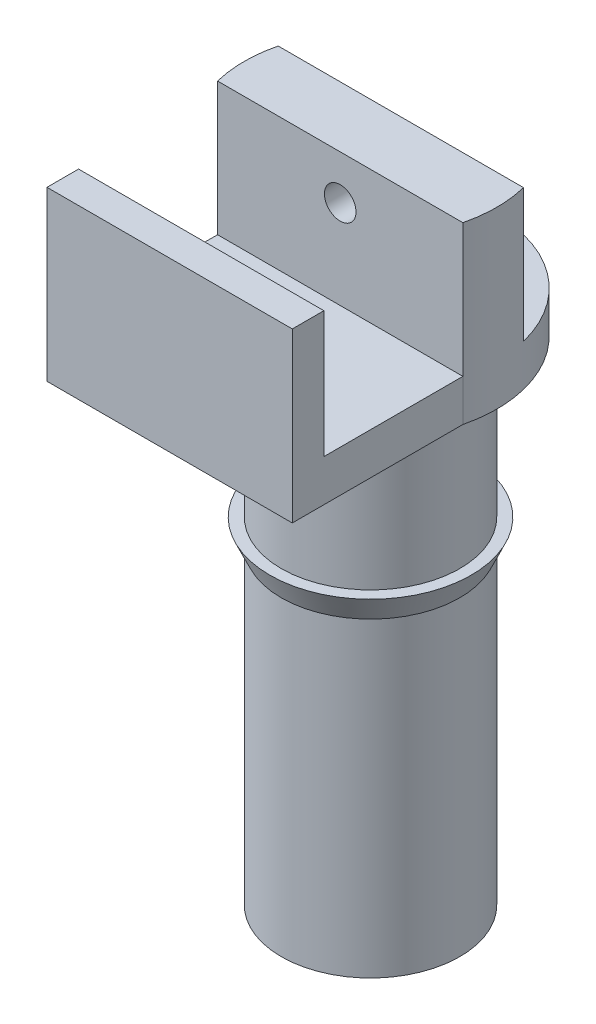
SolidWorks part; units mm, degrees
ref_plane "Front Plane" through (0, 0, 0) normal (0, 0, 1) x (1, 0, 0)
ref_plane "Top Plane" through (0, 0, 0) normal (0, 1, 0) x (1, 0, 0)
ref_plane "Right Plane" through (0, 0, 0) normal (1, 0, 0) x (0, 0, -1)
sketch "Sketch1" plane through (0, 0, 0) normal (0, 1, 0) x (1, 0, 0)
  circle A0 centre (0, 0) radius 17.9497
extrude "Part that goes into base" add sketch "Sketch1" along normal blind 99.06
sketch "Sketch2" plane through (0, 0, 0) normal (0, 0, 1) x (1, 0, 0)
  line L0 (17.9497, 99.06) -> (-17.9497, 99.06) construction
  line L1 (17.9497, 99.06) -> (-17.9497, 99.06)
  line L2 (17.9497, 99.06) -> (17.9497, 67.564) construction
  line L3 (17.9497, 67.564) -> (20.2357, 67.564)
  line L4 (20.2357, 67.564) -> (17.9497, 62.484)
  line L5 (17.9497, 62.484) -> (17.9497, 67.564)
  line L6 (0, 99.06) -> (0, 52.1662) construction
  dimension "D1" = 31.496
  dimension "D2" = 2.286
  dimension "D3" = 5.08
revolve "Clip in mechanism" add sketch "Sketch2" angle 360 about L6 region at (18.7117, 65.8707, 0)
sketch "Sketch3" plane through (0, 99.06, 0) normal (0, 1, 0) x (1, 0, 0)
  circle A0 centre (0, 0) radius 25.4
  dimension "D1" = 50.8
extrude "Boss-Extrude2" add sketch "Sketch3" along normal blind 35.14
ref_plane "Plane1" through (50.8, 0, 0) normal (1, 0, 0) x (0, 0, -1)
sketch "Sketch4" plane through (50.8, 0, 0) normal (1, 0, 0) x (0, 0, -1)
  line L0 (25.4, 134.2) -> (-25.4, 134.2) construction
  line L1 (25.4, 134.2) -> (-25.4, 134.2)
  line L8 (6.096, 134.2) -> (6.096, 107.442)
  line L10 (25.4, 99.06) -> (25.4, 134.2) construction
  line L11 (25.4, 107.442) -> (25.4, 134.2)
  line L12 (6.096, 134.2) -> (25.4, 134.2)
  line L13 (25.4, 107.442) -> (6.096, 107.442)
  line L14 (-25.4, 107.442) -> (-6.096, 107.442)
  line L15 (-25.4, 134.2) -> (-6.096, 134.2)
  line L16 (-25.4, 134.2) -> (-25.4, 107.442)
  line L18 (-6.096, 134.2) -> (-6.096, 107.442)
  dimension "D1" = 8.382
  dimension "D2" = 8.382
  dimension "D4" = 19.304
  dimension "D6" = 19.304
extrude "Cut-Extrude1" cut sketch "Sketch4" against normal through all contours L13 L11 L1 L8 | L18 L1 L16 L14
sketch "Sketch5" plane through (0, 107.442, 0) normal (0, 1, 0) x (1, 0, 0)
  line L0 (-13.191, -27.686) -> (15.1785, -27.686)
  line L1 (24.6576, -6.096) -> (24.6576, -40.386)
  line L2 (-24.6576, -6.096) -> (24.6576, -6.096) construction
  line L3 (-24.6576, -6.096) -> (-24.6576, -40.386)
  line L4 (-24.6576, -40.386) -> (24.6576, -40.386)
  arc A0 (24.6576, -6.096) -> (-24.6576, -6.096) centre (0, 0) cw
  dimension "D1" = 21.59
  dimension "D2" = 34.29
extrude "Boss-Extrude3" add sketch "Sketch5" against normal up to surface (8.382 mm away) contours L3 L4 L1 region at (0, 107.442, 29.7744) up to face at (0, 99.06, 17.9497)
sketch "Sketch6" plane through (0, 107.442, 0) normal (0, 1, 0) x (1, 0, 0)
  line L0 (5.2425, -6.096) -> (5.2425, -34.036)
  line L1 (-24.6576, -6.096) -> (24.6576, -6.096) construction
  line L2 (5.2425, -34.036) -> (-7.0201, -34.036)
  line L3 (-7.0201, -34.036) -> (-24.6576, -34.036)
  line L4 (-24.6576, -6.096) -> (-24.6576, -40.386) construction
  line L5 (-24.6576, -34.036) -> (-24.6576, -40.386)
  line L6 (-24.6576, -40.386) -> (24.6576, -40.386)
  line L7 (24.6576, -40.386) -> (24.6576, -34.036)
  line L8 (24.6576, -6.096) -> (24.6576, -40.386) construction
  line L9 (24.6576, -34.036) -> (5.2425, -34.036)
  dimension "D1" = 27.94
extrude "Boss-Extrude4" add sketch "Sketch6" along normal blind 25.4 contours L2 L3 L5 L6 L7 L9
sketch "Sketch7" plane through (0, 0, -6.096) normal (0, 0, -1) x (-1, 0, 0)
  line L0 (0, 134.2) -> (0, 125.31) construction
  line L1 (24.6576, 134.2) -> (-24.6576, 134.2) construction
  circle A0 centre (0, 125.31) radius 3.175
  dimension "D2" = 6.35
  dimension "D1" = 8.89
extrude "Cut-Extrude2" cut sketch "Sketch7" against normal up to surface (12.192 mm away) up to face at (0, 120.821, 6.096)
